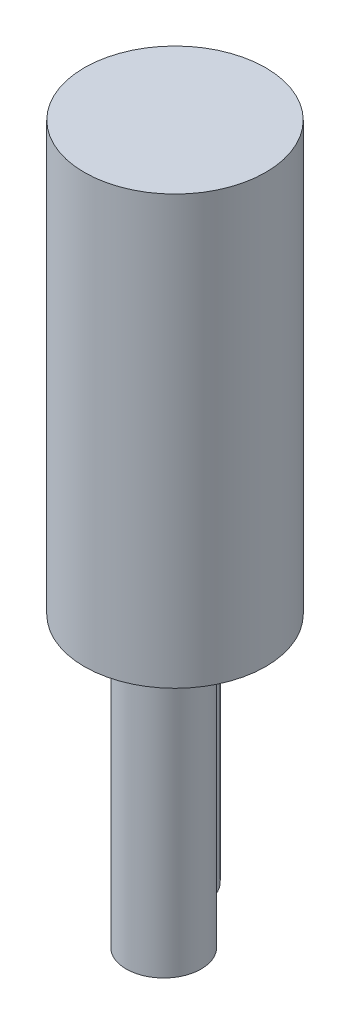
SolidWorks part; units mm, degrees
ref_plane "Front Plane" through (0, 0, 0) normal (0, 0, 1) x (1, 0, 0)
ref_plane "Top Plane" through (0, 0, 0) normal (0, 1, 0) x (1, 0, 0)
ref_plane "Right Plane" through (0, 0, 0) normal (1, 0, 0) x (0, 0, -1)
sketch "Sketch1" plane through (0, 0, 0) normal (0, 1, 0) x (1, 0, 0)
  circle A0 centre (0, 0) radius 169.5
  dimension "D1" = 339
extrude "Boss-Extrude1" add sketch "Sketch1" along normal blind 800
sketch "Sketch2" plane through (0, 0, 0) normal (0, -1, 0) x (1, 0, 0)
  line L0 (120.1655, 146.739) -> (110.4277, 136.3525) construction
  line L1 (-145.2835, -136.3936) -> (-135.5457, -126.007) construction
  line L2 (-208.3417, 278.1378) -> (-194.9407, 292.4316) construction
  line L3 (-310.9675, 168.6753) -> (-297.5664, 182.9692) construction
  line L4 (120.1655, 146.739) -> (110.4277, 136.3525)
  line L5 (-145.2835, -136.3936) -> (-135.5457, -126.007)
  line L6 (-208.3417, 278.1378) -> (-194.9407, 292.4316)
  line L7 (-310.9675, 168.6753) -> (-297.5664, 182.9692)
  line L8 (-367.7025, 235.2958) -> (113.1249, -215.5006) construction
  line L9 (-265.0767, 344.7582) -> (114.3717, -10.991) construction
  line L10 (-135.599, -126.0639) -> (110.4277, 136.3525) construction
  circle A0 centre (-63.8719, -49.5585) radius 70
  circle A1 centre (38.7539, 59.904) radius 70
  point P15 (-63.8719, -49.5585)
  point P21 (38.7539, 59.904)
  point P24 (-304.267, 175.8223)
  dimension "D1" = 140
  dimension "D2" = 140
  dimension "D4" = 71.3467
extrude "Boss-Extrude2" add sketch "Sketch2" along normal blind 490 contours A0 | A1
equation "\"userHeight\"= 2000"
equation "\"hipDiameter\"= 0.191 * \"userHeight\""
equation "\"hipToKneeLength\"= ( 0.53 - 0.285 ) * \"userHeight\""
equation "\"D1@Boss-Extrude2\"=0.245*\"userHeight\""
